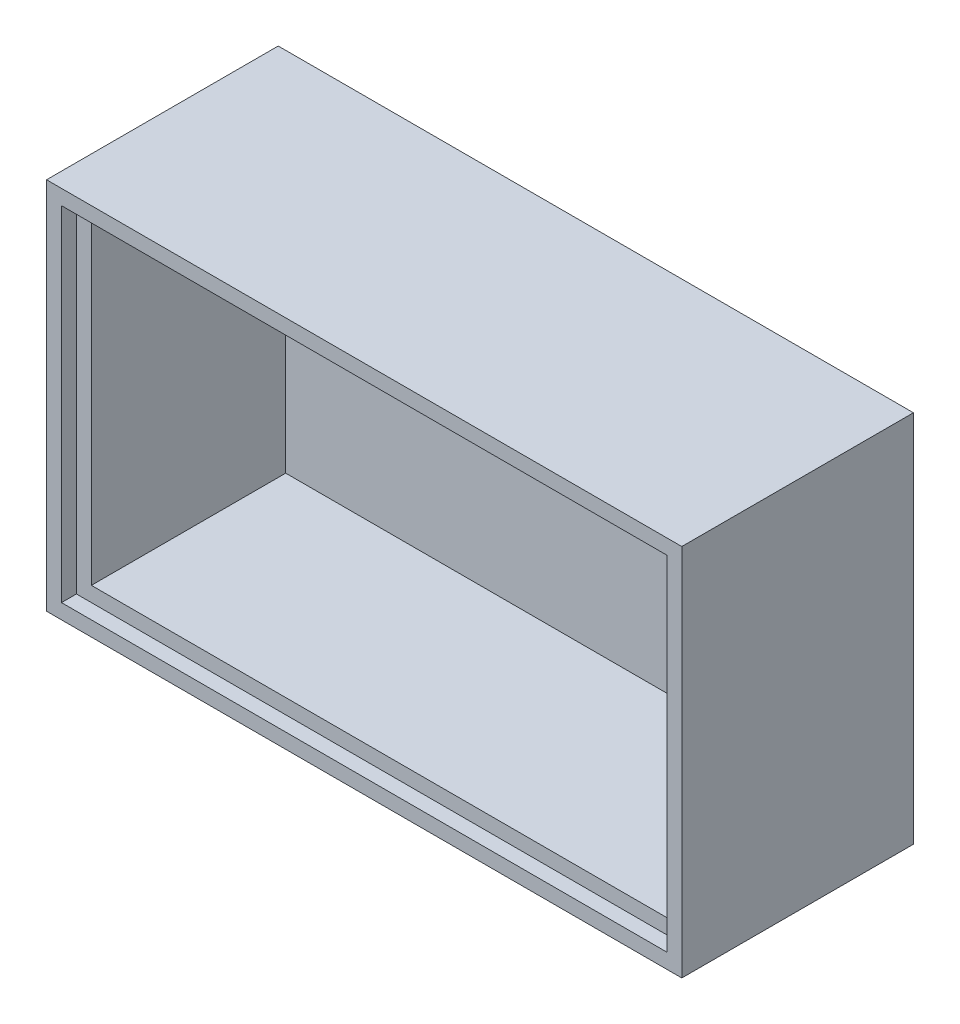
SolidWorks part; units mm, degrees
ref_plane "Přední rovina" through (0, 0, 0) normal (0, 0, 1) x (1, 0, 0)
ref_plane "Horní rovina" through (0, 0, 0) normal (0, 1, 0) x (1, 0, 0)
ref_plane "Pravá rovina" through (0, 0, 0) normal (1, 0, 0) x (0, 0, -1)
sketch "Skica1" plane through (0, 0, 0) normal (0, 0, 1) x (1, 0, 0)
  line L1 (0, 0) -> (85, 0)
  line L2 (0, 0) -> (0, 50)
  line L3 (0, 50) -> (85, 50)
  line L4 (85, 0) -> (85, 50)
  line L5 (2, 48) -> (83, 48)
  line L6 (2, 48) -> (2, 2)
  line L7 (2, 2) -> (83, 2)
  line L8 (83, 48) -> (83, 2)
  line L9 (4, 46) -> (81, 46)
  line L10 (4, 46) -> (4, 4)
  line L11 (4, 4) -> (81, 4)
  line L12 (81, 46) -> (81, 4)
  dimension "D1" = 85
  dimension "D2" = 50
  dimension "D3" = 2
  dimension "D4" = 2
  dimension "D5" = 2
  dimension "D6" = 2
  dimension "D7" = 4
  dimension "D8" = 4
  dimension "D9" = 4
  dimension "D10" = 4
extrude "Přidat vysunutím1" add sketch "Skica1" along normal blind 3 contours L3 L4 L1 L2
extrude "Přidat vysunutím2" add sketch "Skica1<5>" along normal blind 31 contours L1 L4 L3 L2 L5 L8 L7 L6 region at (0.9862, 25, 0)
sketch "Skica1<5>" plane through (0, 0, 0) normal (0, 0, 1) x (1, 0, 0) same geometry as "Skica1"
extrude "Přidat vysunutím3" add sketch "Skica1<6>" along normal blind 29 contours L8 L5 L6 L7 L9 L12 L11 L10 region at (42.5, 47.0685, 0)
sketch "Skica1<6>" plane through (0, 0, 0) normal (0, 0, 1) x (1, 0, 0) same geometry as "Skica1"
